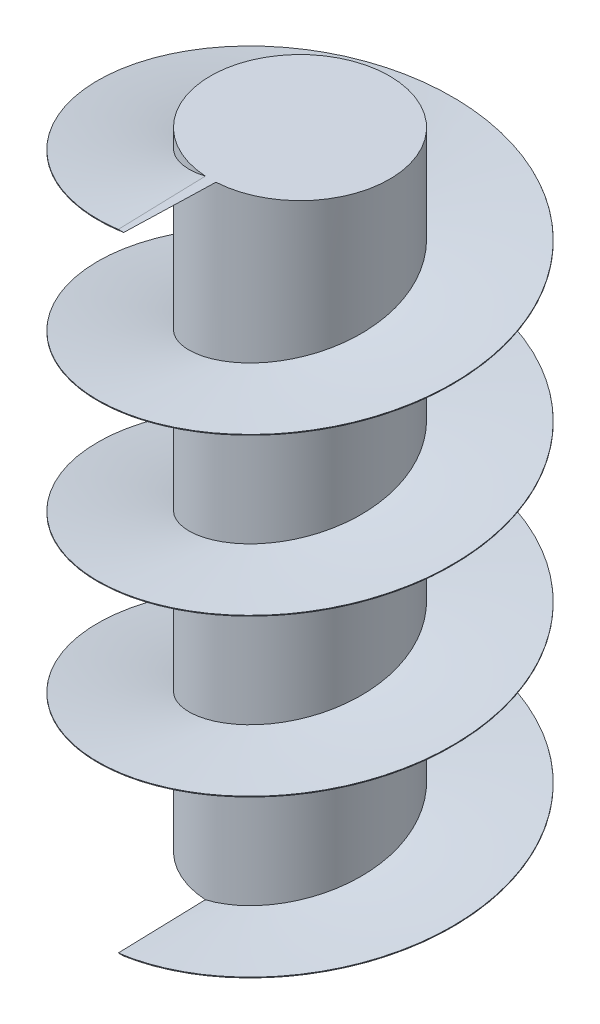
SolidWorks part; units mm, degrees
ref_plane "Front Plane" through (0, 0, 0) normal (0, 0, 1) x (1, 0, 0)
ref_plane "Top Plane" through (0, 0, 0) normal (0, 1, 0) x (1, 0, 0)
ref_plane "Right Plane" through (0, 0, 0) normal (1, 0, 0) x (0, 0, -1)
sketch "Sketch1" plane through (0, 0, 0) normal (0, 1, 0) x (1, 0, 0)
  circle A1 centre (0, 0) radius 10
extrude "Boss-Extrude1" add sketch "Sketch1" along normal blind 70
sketch "Sketch2" plane through (0, 0, 0) normal (0, -1, 0) x (1, 0, 0)
  circle A0 centre (0, 0) radius 20
curve "Helix/Spiral2" pitch 17.5 height 70 radius 20 centre (0, 0, 0) axis (0, 1, 0) start towards (0.7071, 0, 0.7071)
sketch "Sketch4" plane through (0, 0, 0) normal (0, -1, 0) x (1, 0, 0)
  line L0 (0, 0) -> (0, 20) construction
  line L1 (-0.3019, 19.9977) -> (-0.5899, 9.9826)
  line L2 (0.3019, 19.9977) -> (0.5899, 9.9826)
  arc A0 (-0.5899, 9.9826) -> (0.5899, 9.9826) centre (0, 0) cw
  circle A1 centre (0, 0) radius 10 construction
  circle A3 centre (0, 0) radius 20
  arc A4 (0.3019, 19.9977) -> (-0.3019, 19.9977) centre (0, 0) ccw
  point P9 (-1, 19.308)
  point P10 (0, 20.3308)
  point P11 (-0.8, 19.7929)
  point P12 (-0.5899, 9.9826)
  point P13 (-0.3793, 20.0128)
  point P14 (-1.0046, 19.3875)
  point P15 (-0.2889, 19.7463)
  point P16 (-0.2923, 20.3308)
  dimension "D1" = 0
sweep "Sweep1" add profiles "Sketch4" path "Helix/Spiral2"
